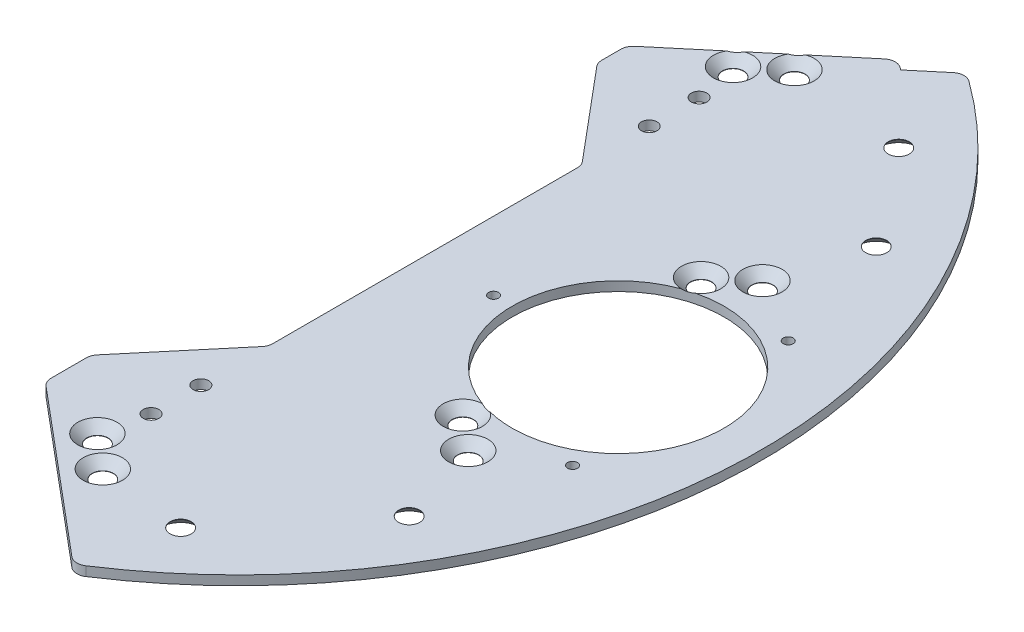
SolidWorks part; units mm, degrees
ref_plane "Plano frontal" through (0, 0, 0) normal (0, 0, 1) x (1, 0, 0)
ref_plane "Plano superior" through (0, 0, 0) normal (0, 1, 0) x (1, 0, 0)
ref_plane "Plano direito" through (0, 0, 0) normal (1, 0, 0) x (0, 0, -1)
sketch "Esboço1" plane through (0, 0, 0) normal (0, 1, 0) x (1, 0, 0)
  line L2 (0, 0) -> (17, 0) construction
  line L3 (17, -85.3229) -> (17, 85.3229)
  arc A0 (17, -85.3229) -> (17, 85.3229) centre (0, 0) ccw
  point P9 (17, 0)
  dimension "D1" = 174
  dimension "D2" = 17
extrude "Ressalto-extrusão1" add sketch "Esboço1" along normal blind 1.5 contours L3 A0
sketch "Esboço2" plane through (0, 1.5, 0) normal (0, 1, 0) x (1, 0, 0)
  line L0 (0, 0) -> (61, 0) construction
  line L1 (61, 0) -> (41, 0) construction
  line L2 (61, 0) -> (71, 17.3205) construction
  line L3 (61, 0) -> (71, -17.3205) construction
  circle A0 centre (61, 0) radius 17
  point P6 (41, 0)
  dimension "D2" = 34
  dimension "D1" = 61
  dimension "D3" = 20
  dimension "D4" = 3
extrude "Corte-extrusão1" cut sketch "Esboço2" against normal through all
hole_wizard "Furo roscado de M21" positions "3DSketch1" profile "Esboço3" tap size "M2" standard "ISO" end condition up to next
sketch3d "3DSketch1"
  point P0 (71, 1.5, 17.3205)
  point P3 (41, 1.5, 0)
  point P6 (71, 1.5, -17.3205)
sketch "Esboço3" plane through (71, 1.5, 17.3205) normal (1, 0, 0) x (0, 0, 1)
  line L0 (0, 0) -> (0, 1.5)
  line L1 (0, 1.5) -> (0.8, 1.5)
  line L2 (0.8, 1.5) -> (0.8, 0)
  line L5 (0.8, 0) -> (0, 0)
  line L11 (0, -6.35) -> (0, 107.95) construction
  dimension "Thru Tap Drill Dia." = 1.6
  dimension "Thru Tap Drill Depth" = 1.5
cosmetic thread "Rosca de furo1" parameters "D2"=2
cosmetic thread "Rosca de furo2" parameters "D2"=2
cosmetic thread "Rosca de furo3" parameters "D2"=2
sketch "Esboço4" plane through (0, 1.5, 0) normal (0, 1, 0) x (1, 0, 0)
  line L0 (0, 0) -> (66.6459, 55.9225) construction
  line L1 (0, 0) -> (61, 0) construction
  line L2 (0, 0) -> (66.6459, -55.9225) construction
  line L3 (50.8976, 74.6906) -> (82.3942, 37.1544) construction
  line L4 (82.3942, 37.1544) -> (70.8874, 27.4991) construction
  line L5 (70.8874, 27.4991) -> (55.1391, 46.2672) construction
  line L6 (55.1391, 46.2672) -> (39.3908, 65.0353) construction
  line L7 (39.3908, 65.0353) -> (50.8976, 74.6906) construction
  line L8 (48.2004, 72.4274) -> (79.697, 34.8912) construction
  line L9 (50.8976, -74.6906) -> (82.3942, -37.1544) construction
  line L10 (82.3942, -37.1544) -> (70.8874, -27.4991) construction
  line L11 (70.8874, -27.4991) -> (39.3908, -65.0353) construction
  line L12 (39.3908, -65.0353) -> (50.8976, -74.6906) construction
  line L13 (63.9487, -53.6593) -> (79.697, -34.8912) construction
  line L14 (63.9487, -53.6593) -> (48.2004, -72.4274) construction
  line L15 (17, -85.3229) -> (17, 85.3229) construction
  line L16 (30, 0) -> (30, 24.445)
  line L17 (29.5321, 25.7306) -> (17, 40.6658)
  line L18 (30, 0) -> (30, -24.445)
  line L19 (29.5321, -25.7306) -> (17, -40.6658)
  line L20 (17, 40.6658) -> (17, -40.6658)
  arc A0 (17, -85.3229) -> (17, 85.3229) centre (0, 0) ccw construction
  arc A1 (30, 24.445) -> (29.5321, 25.7306) centre (28, 24.445) ccw
  arc A2 (30, -24.445) -> (29.5321, -25.7306) centre (28, -24.445) cw
  point P17 (66.6459, -55.9225)
  point P21 (66.6459, 55.9225)
  point P24 (17, 0)
  point P26 (30, 0)
  point P36 (30, 25.173)
  point P39 (30, -25.173)
  dimension "D8" = 2
  dimension "D1" = 40
  dimension "D2" = 40
  dimension "D3" = 49
  dimension "D4" = 11.5
  dimension "D5" = 49
  dimension "D6" = 11.5
  dimension "D7" = 30
extrude "Corte-extrusão2" cut sketch "Esboço4" against normal blind 2.5
sketch "Esboço5" plane through (0, 1.5, 0) normal (0, 1, 0) x (1, 0, 0)
  line L0 (41.7531, 62.2201) -> (68.5252, 30.3144) construction
  line L2 (70.8874, 27.4991) -> (55.1391, 46.2672) construction
  line L3 (41.7531, 62.2201) -> (28.4239, 51.0356) construction
  line L4 (68.5252, 30.3144) -> (55.196, 19.1299) construction
  line L5 (0, 0) -> (66.6459, -55.9225) construction
  line L6 (70.8874, -27.4991) -> (39.3908, -65.0353) construction
  line L7 (41.7531, -62.2201) -> (68.5252, -30.3144) construction
  line L8 (41.7531, -62.2201) -> (28.4239, -51.0356) construction
  line L9 (68.5252, -30.3144) -> (55.196, -19.1299) construction
  point P0 (33.7862, 55.5351)
  point P4 (55.1391, 46.2672)
  point P10 (60.5583, 23.6294)
  point P11 (55.1391, -46.2672)
  point P12 (60.5583, -23.6294)
  point P20 (55.1391, -46.2672)
  point P22 (33.7862, -55.5351)
  dimension "D1" = 41.65
  dimension "D2" = 10.4
  dimension "D3" = 7
  dimension "D4" = 7
  dimension "D5" = 10.4
  dimension "D6" = 41.65
  dimension "D7" = 10.4
  dimension "D8" = 7
  dimension "D9" = 7
  dimension "D10" = 10.4
hole_wizard "Escareado para parafuso com cabeça escareada chata de M32" positions "3DSketch2" profile "Esboço6" countersink size "M3" standard "ISO" end condition up to next
sketch3d "3DSketch2"
  point P0 (33.7862, 1.5, -55.5351)
  point P3 (28.4239, 1.5, -51.0356)
  point P6 (60.5583, 1.5, -23.6294)
  point P9 (55.196, 1.5, -19.1299)
sketch "Esboço6" plane through (33.7862, 1.5, -55.5351) normal (1, 0, 0) x (0, 0, 1)
  line L0 (0, 0) -> (0, 1.5)
  line L1 (0, 1.5) -> (1.7, 1.5)
  line L2 (1.7, 1.5) -> (1.7, 1.45)
  line L3 (1.7, 1.45) -> (3.15, 0)
  line L5 (3.15, 0) -> (0, 0)
  line L6 (-1.7, 1.45) -> (-3.15, 0) construction
  line L11 (0, -6.35) -> (0, 107.95) construction
  dimension "Thru Hole Dia." = 3.4
  dimension "Thru Hole Depth" = 1.5
  dimension "Near C'Sink Dia." = 6.3
  dimension "Near C'Sink Angle" = 90
hole_wizard "Escareado para parafuso com cabeça escareada chata de M33" positions "3DSketch3" profile "Esboço7" countersink size "M3" standard "ISO" end condition up to next
sketch3d "3DSketch3"
  point P0 (55.196, 1.5, 19.1299)
  point P3 (60.5583, 1.5, 23.6294)
  point P6 (28.4239, 1.5, 51.0356)
  point P9 (33.7862, 1.5, 55.5351)
sketch "Esboço7" plane through (55.196, 1.5, 19.1299) normal (1, 0, 0) x (0, 0, 1)
  line L0 (0, 0) -> (0, 1.5)
  line L1 (0, 1.5) -> (1.7, 1.5)
  line L2 (1.7, 1.5) -> (1.7, 1.45)
  line L3 (1.7, 1.45) -> (3.15, 0)
  line L5 (3.15, 0) -> (0, 0)
  line L6 (-1.7, 1.45) -> (-3.15, 0) construction
  line L11 (0, -6.35) -> (0, 107.95) construction
  dimension "Thru Hole Dia." = 3.4
  dimension "Thru Hole Depth" = 1.5
  dimension "Near C'Sink Dia." = 6.3
  dimension "Near C'Sink Angle" = 90
sketch "Esboço8" plane through (0, 1.5, 0) normal (0, 1, 0) x (1, 0, 0)
  line L0 (0, 0) -> (0, 87) construction
  line L1 (27.5, 80) -> (34.1906, 80)
  line L2 (34.1906, 80) -> (34.1906, 87)
  line L3 (34.1906, 87) -> (0, 87)
  line L4 (0, 87) -> (0, 80)
  line L5 (0, 55) -> (27.5, 55)
  line L6 (27.5, 55) -> (27.5, 80)
  line L7 (0, 80) -> (27.5, 80) construction
  line L8 (0, 80) -> (0, 55)
  arc A1 (17, -85.3229) -> (17, 85.3229) centre (0, 0) ccw construction
  point P3 (0, 80)
  point P14 (27.5, 80)
  dimension "D1" = 87
  dimension "D2" = 80
  dimension "D3" = 27.5
  dimension "D4" = 25
sketch "Esboço10" plane through (0, 0, 0) normal (0, -1, 0) x (1, 0, 0)
  line L0 (0, 0) -> (78, 0) construction
  line L1 (0, 0) -> (64.9519, -37.5) construction
  line L2 (0, 0) -> (64.9519, 37.5) construction
  line L3 (0, 0) -> (48.2091, 57.4533) construction
  line L4 (0, 0) -> (53.033, -53.033) construction
  circle A0 centre (61, 0) radius 17 construction
  dimension "D1" = 30
  dimension "D2" = 45
  dimension "D3" = 50
  dimension "D4" = 30
  dimension "D5" = 75
hole_wizard "Escareado para parafuso com cabeça escareada chata de M34" positions "3DSketch4" profile "Esboço11" countersink size "M3" standard "ISO"
sketch3d "3DSketch4"
  point P0 (48.2091, 0, 57.4533)
  point P3 (64.9519, 0, 37.5)
  point P6 (64.9519, 0, -37.5)
  point P9 (53.033, 0, -53.033)
sketch "Esboço11" plane through (48.2091, 0, 57.4533) normal (1, 0, 0) x (0, 0, -1)
  line L0 (0, 0) -> (0, 8.2715)
  line L1 (0, 8.2715) -> (1.7, 7.25)
  line L2 (1.7, 7.25) -> (1.7, 1.45)
  line L3 (1.7, 1.45) -> (3.15, 0)
  line L5 (3.15, 0) -> (0, 0)
  line L6 (-1.7, 1.45) -> (-3.15, 0) construction
  line L10 (0, 8.2715) -> (-1.7, 7.25) construction
  line L11 (0, -6.35) -> (0, 107.95) construction
  dimension "Hole Dia." = 3.4
  dimension "Hole Depth" = 7.25
  dimension "Near C'Sink Dia." = 6.3
  dimension "Near C'Sink Angle" = 90
  dimension "Drill Angle" = 118
sketch "Esboço15" plane through (0, 0, 0) normal (0, -1, 0) x (1, 0, 0)
  line L0 (0, 0) -> (42.4264, 42.4264) construction
  line L1 (0, 0) -> (61, 0)
  line L2 (58.3363, 26.5165) -> (26.5165, 58.3363)
  line L3 (58.3363, 26.5165) -> (40.6586, 8.8388)
  line L4 (40.6586, 8.8388) -> (8.8388, 40.6586)
  line L5 (8.8388, 40.6586) -> (26.5165, 58.3363)
  point P2 (26.5165, 44.1942)
  point P6 (42.4264, 42.4264)
  point P9 (14.4957, 42.0729)
  point P10 (42.0729, 14.4957)
  point P14 (52.6795, 25.1023)
  dimension "D1" = 45
  dimension "D2" = 60
  dimension "D3" = 45
  dimension "D4" = 25
  dimension "D5" = 3
  dimension "D6" = 3
  dimension "D7" = 10
  dimension "D8" = 10
  dimension "D9" = 5
  dimension "D10" = 20
  dimension "D11" = 3
  dimension "D12" = 5
sketch "Esboço17" plane through (0, 0, 0) normal (0, -1, 0) x (1, 0, 0)
  line L0 (28.4239, -51.0356) -> (33.7862, -55.5351) construction
  line L1 (28.4239, -51.0356) -> (26.4956, -53.3337) construction
  line L2 (26.4956, -53.3337) -> (17, -45.366)
  line L4 (17, -40.6658) -> (17, -85.3229) construction
  line L5 (17, -45.366) -> (17, -85.3229)
  line L6 (26.4956, -53.3337) -> (48.7837, -72.0357)
  line L7 (48.7837, -72.0357) -> (48.7837, -85.3229)
  line L8 (48.7837, -85.3229) -> (17, -85.3229)
  arc A0 (17, -85.3229) -> (17, 85.3229) centre (0, 0) ccw construction
  dimension "D1" = 3
extrude "Corte-extrusão3" cut sketch "Esboço17" against normal through all
sketch "Esboço18" plane through (0, 1.5, 0) normal (0, 1, 0) x (1, 0, 0)
  line L0 (33.7862, -55.5351) -> (28.4239, -51.0356) construction
  line L1 (28.4239, -51.0356) -> (25.21, -54.8658) construction
  line L2 (25.21, -54.8658) -> (17, -47.9768)
  line L3 (17, -85.3229) -> (17, -40.6658) construction
  line L4 (17, -47.9768) -> (17, -85.3229)
  line L5 (17, -85.3229) -> (61.5073, -85.3229)
  line L6 (61.5073, -85.3229) -> (25.21, -54.8658)
  dimension "D1" = 5
extrude "Corte-extrusão4" cut sketch "Esboço18" against normal through all contours L5 L6 L2 L4
sketch "Esboço19" plane through (0, 1.5, 0) normal (0, 1, 0) x (1, 0, 0)
  line L0 (48.7837, 72.0357) -> (32.5936, 58.4506) construction
  line L1 (47.042, -73.1851) -> (17, -47.9768) construction
  line L2 (48.7837, 72.0357) -> (46.3908, 70.0278)
  line L3 (44.6312, -71.1622) -> (47.042, -73.1851)
  arc A0 (47.042, -73.1851) -> (48.7837, 72.0357) centre (0, 0) ccw
  arc A1 (47.042, -73.1851) -> (48.7837, 72.0357) centre (0, 0) ccw construction
  arc A2 (46.3908, 70.0278) -> (44.6312, -71.1622) centre (0, 0) cw
  dimension "D1" = 84
extrude "Corte-extrusão5" cut sketch "Esboço19" against normal through all
sketch "Esboço20" plane through (0, 1.5, 0) normal (0, 1, 0) x (1, 0, 0)
  line L0 (41.0285, 65.5283) -> (42.314, 63.9962)
  line L1 (46.3908, 70.0278) -> (32.5936, 58.4506) construction
  line L2 (42.314, 63.9962) -> (48.109, 68.8587)
  line L3 (41.0285, 65.5283) -> (46.8234, 70.3908)
  line L4 (48.109, 68.8587) -> (46.8234, 70.3908)
  arc A0 (44.6312, -71.1622) -> (46.3908, 70.0278) centre (0, 0) ccw construction
  dimension "D1" = 2
  dimension "D2" = 7
extrude "Corte-extrusão6" cut sketch "Esboço20" against normal through all
fillet "Filete2" radius 2 7 edges at (17, 0.75, 40.6658) (17, 0.75, 47.9768) (44.6312, 0.75, 71.1622) (48.109, 0.75, -68.8587) (41.0285, 0.75, -65.5283) (17, 0.75, -40.6658) (17, 0.75, -45.366)
sketch "Esboço21" plane through (0, 1.5, 0) normal (0, 1, 0) x (1, 0, 0)
  line L0 (0, 0) -> (84, 0) construction
  line L1 (0, 0) -> (0, 40) construction
  line L2 (0, 40) -> (30, 40) construction
  line L3 (30, 44) -> (30, 36)
  line L4 (0, 0) -> (0, -40) construction
  line L5 (0, -40) -> (30, -40) construction
  line L6 (30, -44) -> (30, -36)
  arc A0 (45.8838, -70.361) -> (49.3847, 67.9496) centre (0, 0) ccw construction
  point P12 (30, 40)
  point P18 (30, -40)
  dimension "D1" = 40
  dimension "D2" = 30
  dimension "D3" = 8
  dimension "D4" = 40
  dimension "D5" = 30
  dimension "D6" = 8
hole_wizard "Broca de rosquear para tarraxa de M31" positions "3DSketch5" profile "Esboço22" hole size "M3" standard "ISO" end condition through all
sketch3d "3DSketch5"
  point P0 (30, 1.5, 44)
  point P3 (30, 1.5, 36)
  point P6 (30, 1.5, -44)
  point P9 (30, 1.5, -36)
sketch "Esboço22" plane through (30, 1.5, 44) normal (1, 0, 0) x (0, 0, 1)
  line L0 (0, 0) -> (0, 1.5)
  line L1 (0, 1.5) -> (1.25, 1.5)
  line L2 (1.25, 1.5) -> (1.25, 0)
  line L5 (1.25, 0) -> (0, 0)
  line L11 (0, -6.35) -> (0, 107.95) construction
  dimension "Thru Hole Dia." = 2.5
  dimension "Thru Hole Depth" = 1.5
